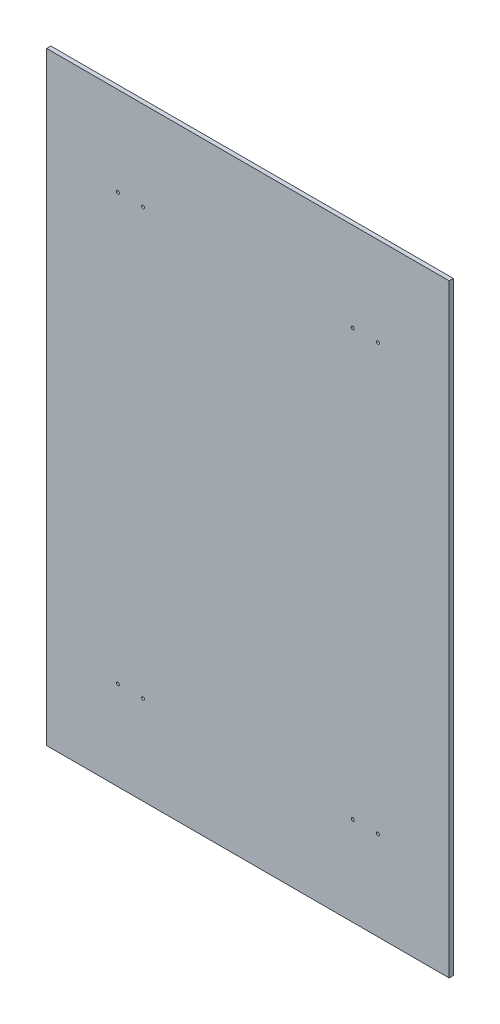
SolidWorks part; units mm, degrees
material "Plain Carbon Steel"
ref_plane "Front Plane" through (0, 0, 0) normal (0, 0, 1) x (1, 0, 0)
ref_plane "Top Plane" through (0, 0, 0) normal (0, 1, 0) x (1, 0, 0)
ref_plane "Right Plane" through (0, 0, 0) normal (1, 0, 0) x (0, 0, -1)
sketch "Sketch1" plane through (0, 0, 0) normal (0, 0, 1) x (1, 0, 0)
  line L1 (-304.8, -457.2) -> (304.8, -457.2)
  line L2 (-304.8, -457.2) -> (-304.8, 457.2)
  line L3 (-304.8, 457.2) -> (304.8, 457.2)
  line L4 (304.8, -457.2) -> (304.8, 457.2)
  line L5 (-304.8, -457.2) -> (304.8, 457.2) construction
  line L6 (-304.8, 457.2) -> (304.8, -457.2) construction
  point P0 (0, 0)
  dimension "D1" = 914.4
  dimension "D2" = 609.6
extrude "Boss-Extrude1" add sketch "Sketch1" along normal mid plane 6.35
sketch "Sketch2" plane through (0, 0, 3.175) normal (0, 0, 1) x (1, 0, 0)
  line L0 (-304.8, -457.2) -> (304.8, -457.2) construction
  line L1 (-304.8, 457.2) -> (-304.8, -457.2) construction
  line L2 (0, 457.2) -> (0, -457.2) construction
  line L3 (304.8, 457.2) -> (-304.8, 457.2) construction
  line L4 (304.8, 0) -> (-304.8, 0) construction
  line L5 (304.8, -457.2) -> (304.8, 457.2) construction
  point P0 (-196.85, -322.2625)
  point P1 (-158.75, -322.2625)
  point P14 (196.85, -322.2625)
  point P15 (158.75, -322.2625)
  point P16 (158.75, 322.2625)
  point P17 (196.85, 322.2625)
  point P18 (-158.75, 322.2625)
  point P19 (-196.85, 322.2625)
  dimension "D1" = 134.9375
  dimension "D2" = 107.95
  dimension "D3" = 38.1
hole_wizard "#8 Clearance Hole1" positions "Sketch2" profile "Sketch3" hole size "#8" standard "ANSI Inch" end condition up to next
sketch "Sketch3" plane through (-196.85, -322.2625, 3.175) normal (1, 0, 0) x (0, -1, 0)
  line L0 (0, 0) -> (0, 6.35)
  line L1 (0, 6.35) -> (2.2479, 6.35)
  line L2 (2.2479, 6.35) -> (2.2479, 0)
  line L5 (2.2479, 0) -> (0, 0)
  line L11 (0, -6.35) -> (0, 107.95) construction
  dimension "Thru Hole Dia." = 4.4958
  dimension "Thru Hole Depth" = 6.35
